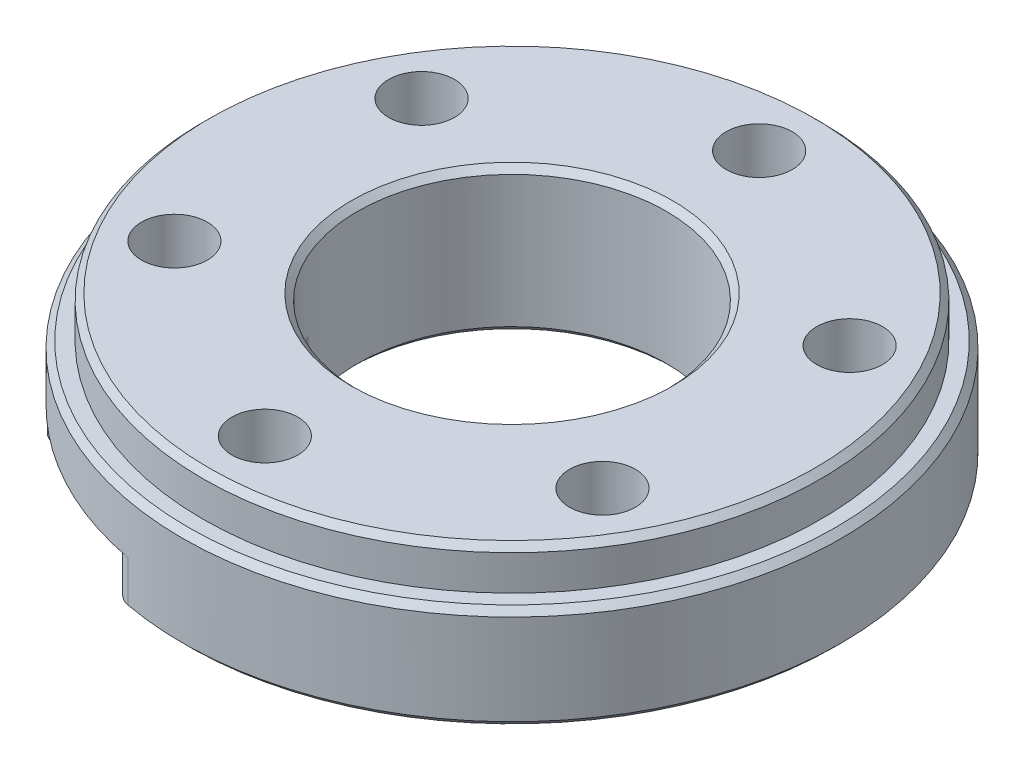
SolidWorks part; units mm, degrees
material "6061 合金"
ref_plane "前视基准面" through (0, 0, 0) normal (0, 0, 1) x (1, 0, 0)
ref_plane "上视基准面" through (0, 0, 0) normal (0, 1, 0) x (1, 0, 0)
ref_plane "右视基准面" through (0, 0, 0) normal (1, 0, 0) x (0, 0, -1)
other "Configuration Table"
sketch "草图1" plane through (0, 0, 0) normal (0, 1, 0) x (1, 0, 0)
  circle A0 centre (0, 0) radius 16
  circle A1 centre (0, 0) radius 7.5
  circle A2 centre (0, 0) radius 12 construction
  circle A3 centre (0, 12) radius 1.6
  circle A4 centre (10.3923, 6) radius 1.6
  circle A5 centre (10.3923, -6) radius 1.6
  circle A6 centre (0, -12) radius 1.6
  circle A7 centre (-10.3923, -6) radius 1.6
  circle A8 centre (-10.3923, 6) radius 1.6
  point P20 (0, 0)
  dimension "D1" = 32
  dimension "D2" = 15
  dimension "D3" = 24
  dimension "D4" = 3.2
  dimension "D5" = 6
extrude "凸台-拉伸1" add sketch "草图1" along normal blind 5
sketch "草图2" plane through (0, 5, 0) normal (0, 1, 0) x (1, 0, 0)
  circle A0 centre (-10.3923, 6) radius 1.6 construction
  circle A1 centre (0, 0) radius 7.5
  circle A2 centre (0, 0) radius 15
  circle A3 centre (0, 0) radius 7.5 construction
  circle A4 centre (-10.3923, -6) radius 1.6 construction
  circle A5 centre (0, -12) radius 1.6 construction
  circle A6 centre (10.3923, -6) radius 1.6 construction
  circle A7 centre (10.3923, 6) radius 1.6 construction
  circle A8 centre (0, 12) radius 1.6 construction
  circle A9 centre (-10.3923, 6) radius 1.6
  circle A10 centre (-10.3923, -6) radius 1.6
  circle A11 centre (0, -12) radius 1.6
  circle A12 centre (10.3923, -6) radius 1.6
  circle A13 centre (10.3923, 6) radius 1.6
  circle A14 centre (0, 12) radius 1.6
  dimension "D1" = 30
extrude "凸台-拉伸2" add sketch "草图2" along normal blind 2
sketch "草图4" plane through (0, 0, 0) normal (0, -1, 0) x (1, 0, 0)
  line L0 (0, 0) -> (-16, 0) construction
  line L2 (-24.257, 1.5) -> (-10, 1.5)
  line L3 (-24.257, 1.5) -> (-24.257, -1.5)
  line L4 (-24.257, -1.5) -> (-10, -1.5)
  line L5 (-10, 1.5) -> (-10, -1.5)
  circle A0 centre (0, 0) radius 16 construction
  dimension "D1" = 10
  dimension "D2" = 1.5
chamfer "倒角2" distance 0.3 angle 45 2 edges at (0, 7, 15) (0, 7, 7.5)
sketch "草图7" plane through (0, 0, 0) normal (0, -1, 0) x (1, 0, 0)
  line L0 (0, 0) -> (-9, 15.5885) construction
  line L1 (-3.4641, -2) -> (-12.4641, 13.5885)
  line L2 (3.4641, 2) -> (-5.5359, 17.5885)
  line L3 (0, 0) -> (-15.1433, 0) construction
  arc A0 (-3.4641, -2) -> (3.4641, 2) centre (0, 0) ccw
  arc A1 (-5.5359, 17.5885) -> (-12.4641, 13.5885) centre (-9, 15.5885) ccw
  point P3 (-4.5, 7.7942)
  dimension "D1" = 8
  dimension "D2" = 60
  dimension "D3" = 18
extrude "切除-拉伸2" cut sketch "草图7" against normal blind 2.3
fillet "圆角2" radius 1 5 edges at (-3.75, 2.3, 6.4952) (0.292, 1.15, 7.4943) (-6.6362, 1.15, 3.4943) (-4.2819, 1.15, 15.4164) (-11.2101, 1.15, 11.4164)
chamfer "倒角3" distance 0.3 angle 45 9 edges at (0, 5, 16) (3.75, 0, -6.4952) (0.3483, 0, 7.6144) (-6.7684, 0, 3.5056) (-1.7899, 0, 11.1002) (-8.7181, 0, 7.1002) (-3.6492, 0, 15.1659) (-11.3094, 0, 10.7432) (8, 0, -13.8564)
sketch "草图11" plane through (0, 0, 0) normal (0, -1, 0) x (1, 0, 0)
  circle A0 centre (0, -12) radius 1.7578
  point P0 (0, -12)
hole_wizard "M3 开槽半沉头螺钉的锥形沉头孔2" positions "草图11" profile "草图12" countersink size "M3" standard "GB"
sketch "草图12" plane through (0, 0, -12) normal (1, 0, 0) x (0, 0, -1)
  line L0 (0, 0) -> (0, 6.9614)
  line L1 (0, 6.9614) -> (1.6, 6)
  line L2 (1.6, 6) -> (1.6, 1.6)
  line L3 (1.6, 1.6) -> (3.2, 0)
  line L5 (3.2, 0) -> (0, 0)
  line L6 (-1.6, 1.6) -> (-3.2, 0) construction
  line L10 (0, 6.9614) -> (-1.6, 6) construction
  line L11 (0, -6.35) -> (0, 107.95) construction
  dimension "孔直径" = 3.2
  dimension "孔深度" = 6
  dimension "近端锥形沉头孔直径" = 6.4
  dimension "近端锥形沉头孔角度" = 90
  dimension "导头角度" = 118
chamfer "倒角4" distance 0.5 angle 45 5 edges at (0, 0, 13.6) (-10.3923, 0, 7.6) (-10.3923, 0, -4.4) (10.3923, 0, -4.4) (10.3923, 0, 7.6)
